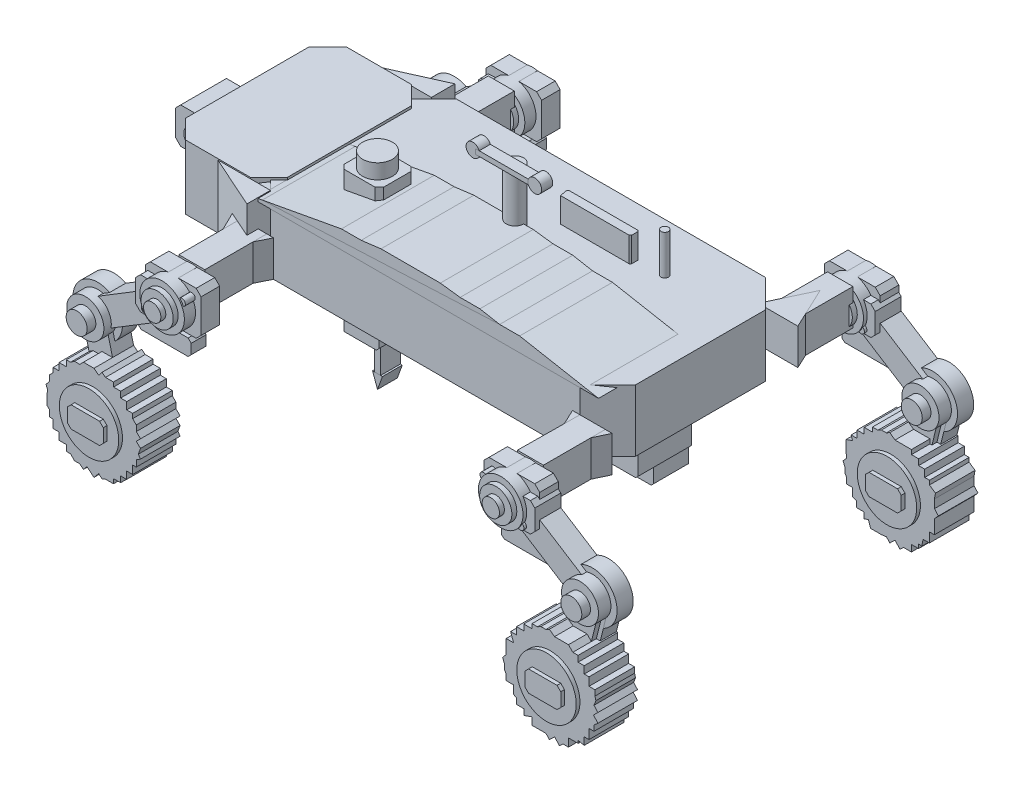
SolidWorks part; units mm, degrees
ref_plane "前视基准面" through (0, 0, 0) normal (0, 0, 1) x (1, 0, 0)
ref_plane "上视基准面" through (0, 0, 0) normal (0, 1, 0) x (1, 0, 0)
ref_plane "右视基准面" through (0, 0, 0) normal (1, 0, 0) x (0, 0, -1)
other "Configuration Table"
ref_plane "v5_near_side_wheel_leg_plane" through (0, 0, 250) normal (0, 0, 1) x (1, 0, 0)
ref_plane "v5_far_side_wheel_leg_plane" through (0, 0, 0) normal (0, 0, 1) x (1, 0, 0)
sketch "草图1" plane through (0, 0, 0) normal (0, 1, 0) x (1, 0, 0)
  line L0 (-225, -150) -> (275, -150)
  line L1 (275, -150) -> (320, -105)
  line L2 (320, -105) -> (320, 105)
  line L3 (320, 105) -> (275, 150)
  line L4 (275, 150) -> (-225, 150)
  line L5 (-225, 150) -> (-270, 105)
  line L6 (-270, 105) -> (-270, -105)
  line L7 (-270, -105) -> (-225, -150)
extrude "v5_1_thicker_chamfered_main_chassis" add sketch "草图1" along normal blind 100 separate body
sketch "草图2" plane through (0, 0, 0) normal (0, 1, 0) x (1, 0, 0)
  line L0 (-382.5, -130) -> (-277.5, -130)
  line L1 (-277.5, -130) -> (-247.5, -100)
  line L2 (-247.5, -100) -> (-247.5, 100)
  line L3 (-247.5, 100) -> (-277.5, 130)
  line L4 (-277.5, 130) -> (-382.5, 130)
  line L5 (-382.5, 130) -> (-412.5, 100)
  line L6 (-412.5, 100) -> (-412.5, -100)
  line L7 (-412.5, -100) -> (-382.5, -130)
extrude "v5_1_projecting_front_sensor_head" add sketch "草图2" along normal blind 104 separate body
sketch "草图3" plane through (0, 0, 0) normal (0, 1, 0) x (1, 0, 0)
  line L0 (-330, 130) -> (-245, 130)
  line L1 (-277.5, 130) -> (-382.5, 130) construction
  line L2 (-225, 150) -> (-270, 105) construction
  line L3 (-245, 130) -> (-245, 168)
  line L4 (-245, 168) -> (-330, 130)
extrude "v5_7_front_near_shoulder_diagonal_fill_no_gap" add sketch "草图3" along normal blind 102 separate body
sketch "草图4" plane through (0, 0, 0) normal (0, 1, 0) x (1, 0, 0)
  line L0 (-330, -130) -> (-245, -130)
  line L1 (-382.5, -130) -> (-277.5, -130) construction
  line L2 (-270, -105) -> (-225, -150) construction
  line L3 (-245, -130) -> (-245, -168)
  line L4 (-245, -168) -> (-330, -130)
extrude "v5_7_front_far_shoulder_diagonal_fill_no_gap" add sketch "草图4" along normal blind 102 separate body
sketch "草图5" plane through (0, 0, 0) normal (0, 1, 0) x (1, 0, 0)
  line L0 (-273, 150) -> (-231, 150)
  line L1 (-231, 150) -> (-231, 250)
  line L2 (-231, 250) -> (-273, 250)
  line L3 (-273, 250) -> (-273, 150)
extrude "v5_17_front_near_side_100mm_outboard_beam_connected" add sketch "草图5" along normal blind 58 separate body
sketch "草图6" plane through (0, 0, 0) normal (0, 1, 0) x (1, 0, 0)
  line L0 (275, 150) -> (316, 150)
  line L1 (316, 150) -> (316, 250)
  line L2 (316, 250) -> (275, 250)
  line L3 (275, 250) -> (275, 150)
extrude "v5_17_rear_near_side_100mm_outboard_beam_connected" add sketch "草图6" along normal blind 58 separate body
sketch "草图7" plane through (0, 0, 0) normal (0, 1, 0) x (1, 0, 0)
  line L0 (-273, -250) -> (-231, -250)
  line L1 (-263.525, -250) -> (263.525, -250) construction
  line L2 (-231, -250) -> (-231, -150)
  line L3 (-231, -150) -> (-273, -150)
  line L4 (-273, -150) -> (-273, -250)
extrude "v5_17_front_far_side_100mm_outboard_beam_connected" add sketch "草图7" along normal blind 58 separate body
sketch "草图8" plane through (0, 0, 0) normal (0, 1, 0) x (1, 0, 0)
  line L0 (274, -250) -> (316, -250)
  line L1 (-263.525, -250) -> (263.525, -250) construction
  line L2 (316, -250) -> (316, -150)
  line L3 (316, -150) -> (275, -150)
  line L4 (275, -150) -> (274, -250)
extrude "v5_17_rear_far_side_100mm_outboard_beam_connected" add sketch "草图8" along normal blind 58 separate body
sketch "草图9" plane through (0, 0, 0) normal (0, 1, 0) x (1, 0, 0)
  line L0 (-287.5, 149) -> (-220, 150)
  line L1 (-245, 168) -> (-330, 130) construction
  line L2 (275, 150) -> (-225, 150) construction
  line L3 (-220, 150) -> (-253.75, 218)
  line L4 (-253.75, 218) -> (-287.5, 149)
extrude "v5_13_front_near_side_compact_root_gusset" add sketch "草图9" along normal blind 58 separate body
sketch "草图10" plane through (0, 0, 0) normal (0, 1, 0) x (1, 0, 0)
  line L0 (263, 150) -> (327, 150)
  line L1 (275, 150) -> (-225, 150) construction
  line L2 (327, 150) -> (295, 218)
  line L3 (295, 218) -> (263, 150)
extrude "v5_13_rear_near_side_compact_root_gusset" add sketch "草图10" along normal blind 58 separate body
sketch "草图11" plane through (0, 0, 0) normal (0, 1, 0) x (1, 0, 0)
  line L0 (-287.5, -149) -> (-220, -150)
  line L1 (-330, -130) -> (-245, -168) construction
  line L2 (-225, -150) -> (275, -150) construction
  line L3 (-220, -150) -> (-253.75, -218)
  line L4 (-253.75, -218) -> (-287.5, -149)
extrude "v5_13_front_far_side_compact_root_gusset" add sketch "草图11" along normal blind 58 separate body
sketch "草图12" plane through (0, 0, 0) normal (0, 1, 0) x (1, 0, 0)
  line L0 (263, -150) -> (327, -150)
  line L1 (-225, -150) -> (275, -150) construction
  line L2 (327, -150) -> (295, -218)
  line L3 (295, -218) -> (263, -150)
extrude "v5_13_rear_far_side_compact_root_gusset" add sketch "草图12" along normal blind 58 separate body
sketch "草图13" plane through (0, 0, 0) normal (0, 0, 1) x (1, 0, 0)
  line L0 (-270, 96) -> (305, 96)
  line L1 (305, 96) -> (273.0556, 101.904)
  line L2 (273.0556, 101.904) -> (241.1432, 107.8022)
  line L3 (241.1432, 107.8022) -> (209.2939, 113.6886)
  line L4 (209.2939, 113.6886) -> (177.537, 119.558)
  line L5 (177.537, 119.558) -> (145.2778, 119.558)
  line L6 (145.2778, 119.558) -> (113.3333, 125.4449)
  line L7 (113.3333, 125.4449) -> (81.3889, 125.4449)
  line L8 (81.3889, 125.4449) -> (49.4444, 129.4835)
  line L9 (49.4444, 129.4835) -> (17.5, 129.4835)
  line L10 (17.5, 129.4835) -> (-14.4444, 129.4835)
  line L11 (-14.4444, 129.4835) -> (-46.3889, 129.4835)
  line L12 (-46.3889, 129.4835) -> (-78.3333, 125.4449)
  line L13 (-78.3333, 125.4449) -> (-110.2778, 125.4449)
  line L14 (-110.2778, 125.4449) -> (-142.2222, 119.558)
  line L15 (-142.2222, 119.558) -> (-174.0716, 113.6886)
  line L16 (-174.0716, 113.6886) -> (-206.0136, 107.8022)
  line L17 (-206.0136, 107.8022) -> (-238.019, 101.904)
  line L18 (-238.019, 101.904) -> (-270, 96)
extrude "v5_1_near_segmented_curved_upper_shell" add sketch "草图13" along normal blind 150 separate body
sketch "草图14" plane through (0, 0, 0) normal (0, 0, 1) x (1, 0, 0)
  line L0 (-270, 96) -> (305, 96)
  line L1 (305, 96) -> (273.0556, 101.904)
  line L2 (305, 96) -> (177.537, 119.558) construction
  line L3 (273.0556, 101.904) -> (241.2685, 107.779)
  line L4 (241.2685, 107.779) -> (209.2939, 113.6886)
  line L5 (209.2939, 113.6886) -> (177.537, 119.558)
  line L6 (177.537, 119.558) -> (145.2778, 119.558)
  line L7 (145.2778, 119.558) -> (113.3333, 125.4449)
  line L8 (113.3333, 125.4449) -> (81.3889, 125.4449)
  line L9 (81.3889, 125.4449) -> (49.4444, 129.4835)
  line L10 (49.4444, 129.4835) -> (17.5, 129.4835)
  line L11 (49.4444, 129.4835) -> (-46.3889, 129.4835) construction
  line L12 (17.5, 129.4835) -> (-14.4444, 129.4835)
  line L13 (-14.4444, 129.4835) -> (-46.3889, 129.4835)
  line L14 (-46.3889, 129.4835) -> (-78.3333, 125.4449)
  line L15 (-78.3333, 125.4449) -> (-110.2778, 125.4449)
  line L16 (-110.2778, 125.4449) -> (-142.2222, 119.558)
  line L17 (-110.2778, 125.4449) -> (-238.019, 101.904) construction
  line L18 (-142.2222, 119.558) -> (-174.1484, 113.6745)
  line L19 (-174.1484, 113.6745) -> (-206.1393, 107.779)
  line L20 (-206.1393, 107.779) -> (-238.019, 101.904)
  line L21 (-238.019, 101.904) -> (-270, 96)
extrude "v5_1_far_segmented_curved_upper_shell" add sketch "草图14" along normal blind 150 flip side to cut separate body
sketch "草图15" plane through (0, 0, 0) normal (0, 0, 1) x (1, 0, 0)
  line L0 (10.5, 14) -> (199.5, 14)
  line L1 (199.5, 14) -> (207.5, 22)
  line L2 (207.5, 22) -> (207.5, 82)
  line L3 (207.5, 82) -> (199.5, 90)
  line L4 (199.5, 90) -> (10.5, 90)
  line L5 (10.5, 90) -> (0, 79.5)
  line L6 (0, 79.5) -> (0, 22)
  line L7 (0, 22) -> (10.5, 14)
extrude "v5_1_recessed_side_panel_frame" add sketch "草图15" along normal blind 74 separate body
sketch "草图16" plane through (0, 0, 0) normal (0, 0, 1) x (1, 0, 0)
  line L0 (31, 28) -> (179, 28)
  line L1 (179, 28) -> (184, 33)
  line L2 (184, 33) -> (184, 75)
  line L3 (184, 75) -> (179, 80)
  line L4 (179, 80) -> (31, 80)
  line L5 (31, 80) -> (26, 75)
  line L6 (26, 75) -> (26, 33)
  line L7 (26, 33) -> (31, 28)
extrude "v5_1_battery_electronics_panel_insert" add sketch "草图16" along normal blind 82 separate body
sketch "草图17" plane through (0, 0, 0) normal (0, 0, 1) x (1, 0, 0)
  line L0 (-191, -49) -> (301, -49)
  line L1 (301, -49) -> (305, -45)
  line L2 (305, -45) -> (305, 9)
  line L3 (305, 9) -> (301, 13)
  line L4 (301, 13) -> (-191, 13)
  line L5 (-191, 13) -> (-195, 9)
  line L6 (-195, 9) -> (-195, -45)
  line L7 (-195, -45) -> (-191, -49)
extrude "v5_7_integrated_lower_side_skirt_no_long_gap" add sketch "草图17" along normal blind 86
sketch "草图18" plane through (0, 0, 0) normal (0, 0, 1) x (1, 0, 0)
  line L0 (-135, -76) -> (15, -76)
  line L1 (15, -76) -> (20, -71)
  line L2 (20, -71) -> (20, -37)
  line L3 (20, -37) -> (15, -32)
  line L4 (15, -32) -> (-135, -32)
  line L5 (-135, -32) -> (-140, -37)
  line L6 (-140, -37) -> (-140, -71)
  line L7 (-140, -71) -> (-135, -76)
extrude "v5_7_protected_underbody_payload_bay_joined" add sketch "草图18" along normal blind 60
sketch "草图19" plane through (0, 0, 0) normal (0, 0, 1) x (1, 0, 0)
  line L0 (-181, -77) -> (-159, -77)
  line L1 (-159, -77) -> (-155, -73)
  line L2 (-155, -73) -> (-155, -15)
  line L3 (-155, -15) -> (-159, -11)
  line L4 (-159, -11) -> (-181, -11)
  line L5 (-181, -11) -> (-185, -15)
  line L6 (-185, -15) -> (-185, -73)
  line L7 (-185, -73) -> (-181, -77)
extrude "v5_7_front_skid_vertical_support_joined" add sketch "草图19" along normal blind 56
sketch "草图20" plane through (0, 0, 0) normal (0, 0, 1) x (1, 0, 0)
  line L0 (29, -77) -> (51, -77)
  line L1 (51, -77) -> (55, -73)
  line L2 (55, -73) -> (55, -15)
  line L3 (55, -15) -> (51, -11)
  line L4 (51, -11) -> (29, -11)
  line L5 (29, -11) -> (25, -15)
  line L6 (25, -15) -> (25, -73)
  line L7 (25, -73) -> (29, -77)
extrude "v5_7_center_skid_vertical_support_joined" add sketch "草图20" along normal blind 56
sketch "草图21" plane through (0, 0, 0) normal (0, 0, 1) x (1, 0, 0)
  line L0 (274, -77) -> (296, -77)
  line L1 (296, -77) -> (300, -73)
  line L2 (300, -73) -> (300, -15)
  line L3 (300, -15) -> (296, -11)
  line L4 (296, -11) -> (274, -11)
  line L5 (274, -11) -> (270, -15)
  line L6 (270, -15) -> (270, -73)
  line L7 (270, -73) -> (274, -77)
extrude "v5_7_rear_skid_vertical_support_joined" add sketch "草图21" along normal blind 56
sketch "草图22" plane through (0, 0, 0) normal (0, 0, 1) x (1, 0, 0)
  line L0 (-446, 35) -> (-338, 35)
  line L1 (-338, 35) -> (-330, 43)
  line L2 (-330, 43) -> (-330, 85)
  line L3 (-330, 85) -> (-338, 93)
  line L4 (-338, 93) -> (-446, 93)
  line L5 (-446, 93) -> (-454, 85)
  line L6 (-454, 85) -> (-454, 43)
  line L7 (-454, 43) -> (-446, 35)
extrude "v5_1_front_stereo_camera_bezel" add sketch "草图22" along normal blind 74 separate body
sketch "草图23" plane through (0, 0, 0) normal (0, 0, 1) x (1, 0, 0)
  circle A0 centre (-416, 66) radius 15
extrude "v5_1_left_rgb_camera_lens" add sketch "草图23" along normal blind 84 separate body
sketch "草图24" plane through (0, 0, 0) normal (0, 0, 1) x (1, 0, 0)
  circle A0 centre (-370, 66) radius 15
extrude "v5_1_right_depth_camera_lens" add sketch "草图24" along normal blind 84 separate body
sketch "草图25" plane through (0, 0, 250) normal (0, 0, 1) x (1, 0, 0)
  line L0 (-289, -15) -> (-215, -15)
  line L1 (-215, -15) -> (-207, -7)
  line L2 (-207, -7) -> (-207, 47)
  line L3 (-207, 47) -> (-215, 55)
  line L4 (-215, 55) -> (-289, 55)
  line L5 (-289, 55) -> (-297, 47)
  line L6 (-297, 47) -> (-297, -7)
  line L7 (-297, -7) -> (-289, -15)
extrude "front_near_leg_side_hip_mount_plate" add sketch "草图25" along normal blind 30 separate body
sketch "草图26" plane through (0, 0, 250) normal (0, 0, 1) x (1, 0, 0)
  line L0 (-293, -11) -> (-246, -11)
  line L1 (-297, -7) -> (-289, -15) construction
  line L2 (-246, -11) -> (-238, -3)
  line L3 (-238, -3) -> (-238, 33)
  line L4 (-238, 33) -> (-246, 41)
  line L5 (-246, 41) -> (-293, 41)
  line L6 (-293, 41) -> (-301, 33)
  line L7 (-301, 33) -> (-301, -3)
  line L8 (-301, -3) -> (-293, -11)
extrude "front_near_leg_side_fork_clevis_block" add sketch "草图26" along normal blind 42 separate body
sketch "草图27" plane through (0, 0, 250) normal (0, 0, 1) x (1, 0, 0)
  line L0 (-310, -53) -> (-234, -53)
  line L1 (-234, -53) -> (-229, -48)
  line L2 (-229, -48) -> (-229, -32)
  line L3 (-229, -32) -> (-234, -27)
  line L4 (-234, -27) -> (-310, -27)
  line L5 (-310, -27) -> (-315, -32)
  line L6 (-315, -32) -> (-315, -48)
  line L7 (-315, -48) -> (-310, -53)
extrude "front_near_leg_side_chamfered_gusset_block" add sketch "草图27" along normal blind 24 separate body
sketch "草图28" plane through (0, 0, 250) normal (0, 0, 1) x (1, 0, 0)
  circle A0 centre (-222, 40) radius 5.5
extrude "front_near_leg_side_upper_mount_bolt" add sketch "草图28" along normal blind 46 separate body
sketch "草图29" plane through (0, 0, 250) normal (0, 0, 1) x (1, 0, 0)
  circle A0 centre (-282, 0) radius 5.5
extrude "front_near_leg_side_lower_mount_bolt" add sketch "草图29" along normal blind 46 separate body
sketch "草图30" plane through (0, 0, 250) normal (0, 0, 1) x (1, 0, 0)
  line L0 (-241.2798, 0) -> (-367.2798, -76.8843)
  line L1 (-367.2798, -76.8843) -> (-388.1117, -42.7445)
  line L2 (-388.1117, -42.7445) -> (-261.3348, 34.6139)
  line L3 (-261.3348, 34.6139) -> (-241.2798, 0)
extrude "front_near_leg_side_upper_parallel_link" add sketch "草图30" along normal blind 34 separate body
sketch "草图31" plane through (0, 0, 250) normal (0, 0, 1) x (1, 0, 0)
  line L0 (-262.1759, 0) -> (-388.1759, -77.5979)
  line L1 (-388.1759, -77.5979) -> (-397.614, -62.2727)
  line L2 (-397.614, -62.2727) -> (-270.7515, 15.8564)
  line L3 (-270.7515, 15.8564) -> (-262.1759, 0)
extrude "front_near_leg_side_inner_upper_link" add sketch "草图31" along normal blind 26 separate body
sketch "草图32" plane through (0, 0, 250) normal (0, 0, 1) x (1, 0, 0)
  line L0 (-358.5971, -55.1493) -> (-328.5971, -175.1493)
  line L1 (-328.5971, -175.1493) -> (-367.4029, -184.8507)
  line L2 (-367.4029, -184.8507) -> (-396.4049, -64.2361)
  line L3 (-397.614, -62.2727) -> (-388.1759, -77.5979) construction
  line L4 (-396.4049, -64.2361) -> (-358.5971, -55.1493)
extrude "front_near_leg_side_lower_parallel_link" add sketch "草图32" along normal blind 34 separate body
sketch "草图33" plane through (0, 0, 250) normal (0, 0, 1) x (1, 0, 0)
  line L0 (-384.2687, -67.8172) -> (-354.2687, -187.8172)
  line L1 (-354.2687, -187.8172) -> (-369.2687, -191.5672)
  line L2 (-369.2687, -191.5672) -> (-399.2687, -71.5672)
  line L3 (-399.2687, -71.5672) -> (-384.2687, -67.8172)
extrude "front_near_leg_side_inner_lower_link" add sketch "草图33" along normal blind 26 separate body
sketch "草图34" plane through (0, 0, 250) normal (0, 0, 1) x (1, 0, 0)
  circle A0 centre (-252, 20) radius 36
extrude "front_near_leg_side_hip_joint_pod" add sketch "草图34" along normal blind 48 separate body
sketch "草图35" plane through (0, 0, 250) normal (0, 0, 1) x (1, 0, 0)
  circle A0 centre (-252, 20) radius 26
extrude "front_near_leg_side_hip_angle_control_washer" add sketch "草图35" along normal blind 56 separate body
sketch "草图36" plane through (0, 0, 250) normal (0, 0, 1) x (1, 0, 0)
  circle A0 centre (-252, 20) radius 14
extrude "front_near_leg_side_hip_pin_cap" add sketch "草图36" along normal blind 64 separate body
sketch "草图37" plane through (0, 0, 250) normal (0, 0, 1) x (1, 0, 0)
  circle A0 centre (-378, -60) radius 30
extrude "front_near_leg_side_knee_joint_pod" add sketch "草图37" along normal blind 46 separate body
sketch "草图38" plane through (0, 0, 250) normal (0, 0, 1) x (1, 0, 0)
  circle A0 centre (-378, -60) radius 40
extrude "front_near_leg_side_knee_outer_angle_plate" add sketch "草图38" along normal blind 26 separate body
sketch "草图39" plane through (0, 0, 250) normal (0, 0, 1) x (1, 0, 0)
  circle A0 centre (-378, -60) radius 17
extrude "front_near_leg_side_knee_pin_cap" add sketch "草图39" along normal blind 60 separate body
sketch "草图40" plane through (0, 0, 250) normal (0, 0, 1) x (1, 0, 0)
  line L0 (-367.4029, -184.8507) -> (-328.5971, -175.1493) construction
  circle A0 centre (-348, -180) radius 30
extrude "front_near_leg_side_axle_joint_pod" add sketch "草图40" along normal blind 46 separate body
sketch "草图41" plane through (0, 0, 250) normal (0, 0, 1) x (1, 0, 0)
  circle A0 centre (-348, -180) radius 21
extrude "front_near_leg_side_axle_pin_cap" add sketch "草图41" along normal blind 58 separate body
sketch "草图42" plane through (0, 0, 250) normal (0, 0, 1) x (1, 0, 0)
  line L0 (-271, -180) -> (-277.6506, -173.3494)
  line L1 (-277.6506, -173.3494) -> (-270.8793, -166.5782)
  line L2 (-270.8793, -166.5782) -> (-277.6506, -159.807)
  line L3 (-277.6506, -159.807) -> (-277.6506, -150.5334)
  line L4 (-277.6506, -150.5334) -> (-283.5183, -144.6656)
  line L5 (-283.5183, -144.6656) -> (-283.5183, -137.2211)
  line L6 (-283.5183, -137.2211) -> (-293.1163, -137.2211)
  line L7 (-293.1163, -137.2211) -> (-293.1163, -125.5528)
  line L8 (-293.1163, -125.5528) -> (-302.9581, -125.5528)
  line L9 (-302.9581, -125.5528) -> (-302.9581, -115.9768)
  line L10 (-302.9581, -115.9768) -> (-314.5308, -115.9768)
  line L11 (-314.5308, -115.9768) -> (-314.5308, -108.8613)
  line L12 (-314.5308, -108.8613) -> (-327.3898, -108.8613)
  line L13 (-327.3898, -108.8613) -> (-332.978, -104.4795)
  line L14 (-332.978, -104.4795) -> (-338.4088, -111.4056)
  line L15 (-338.4088, -111.4056) -> (-346.0263, -105.4328)
  line L16 (-328.5971, -175.1493) -> (-358.5971, -55.1493) construction
  line L17 (-346.0263, -105.4328) -> (-354.9592, -105.4328)
  line L18 (-354.9592, -105.4328) -> (-363.022, -105.4328)
  line L19 (-363.022, -105.4328) -> (-368.9948, -111.4056)
  line L20 (-368.9948, -111.4056) -> (-377.4666, -111.4056)
  line L21 (-377.4666, -111.4056) -> (-383.9637, -115.9768)
  line L22 (-396.4049, -64.2361) -> (-367.4029, -184.8507) construction
  line L23 (-383.9637, -115.9768) -> (-390.7789, -115.9768)
  line L24 (-390.7789, -115.9768) -> (-390.7789, -125.5528)
  line L25 (-390.7789, -125.5528) -> (-402.4472, -125.5528)
  line L26 (-402.4472, -125.5528) -> (-402.4472, -137.2211)
  line L27 (-402.4472, -137.2211) -> (-412.0232, -137.2211)
  line L28 (-412.0232, -137.2211) -> (-412.0232, -144.6656)
  line L29 (-412.0232, -144.6656) -> (-417.891, -150.5334)
  line L30 (-417.891, -150.5334) -> (-417.891, -159.807)
  line L31 (-417.891, -159.807) -> (-423.5205, -166.5782)
  line L32 (-423.5205, -166.5782) -> (-420.7057, -173.3494)
  line L33 (-420.7057, -173.3494) -> (-422.1131, -180)
  line L34 (-422.1131, -180) -> (-422.1131, -186.9592)
  line L35 (-422.1131, -186.9592) -> (-422.1131, -195.022)
  line L36 (-422.1131, -195.022) -> (-417.891, -199.2441)
  line L37 (-417.891, -199.2441) -> (-417.891, -209.4666)
  line L38 (-417.891, -209.4666) -> (-412.0232, -209.4666)
  line L39 (-412.0232, -209.4666) -> (-412.0232, -222.7789)
  line L40 (-412.0232, -222.7789) -> (-402.4472, -222.7789)
  line L41 (-402.4472, -222.7789) -> (-402.4472, -234.4472)
  line L42 (-402.4472, -234.4472) -> (-390.7789, -234.4472)
  line L43 (-390.7789, -234.4472) -> (-390.7789, -244.0232)
  line L44 (-390.7789, -244.0232) -> (-383.9637, -244.0232)
  line L45 (-383.9637, -244.0232) -> (-377.4666, -250.5203)
  line L46 (-377.4666, -250.5203) -> (-368.9948, -250.5203)
  line L47 (-368.9948, -250.5203) -> (-363.022, -255.5205)
  line L48 (-363.022, -255.5205) -> (-357.3064, -248.6931)
  line L49 (-357.3064, -248.6931) -> (-346.0263, -258.1364)
  line L50 (-346.0263, -258.1364) -> (-338.4088, -249.0371)
  line L51 (-338.4088, -249.0371) -> (-332.978, -253.5835)
  line L52 (-332.978, -253.5835) -> (-327.3898, -251.3103)
  line L53 (-327.3898, -251.3103) -> (-314.5308, -251.3103)
  line L54 (-314.5308, -251.3103) -> (-314.5308, -244.0232)
  line L55 (-314.5308, -244.0232) -> (-302.9581, -244.0232)
  line L56 (-302.9581, -244.0232) -> (-302.9581, -234.4472)
  line L57 (-302.9581, -234.4472) -> (-293.1163, -234.4472)
  line L58 (-293.1163, -234.4472) -> (-293.1163, -222.7789)
  line L59 (-293.1163, -222.7789) -> (-283.5183, -222.7789)
  line L60 (-283.5183, -222.7789) -> (-283.5183, -209.4666)
  line L61 (-283.5183, -209.4666) -> (-277.6506, -209.4666)
  line L62 (-277.6506, -209.4666) -> (-277.6506, -199.2441)
  line L63 (-277.6506, -199.2441) -> (-271, -195.022)
  line L64 (-271, -195.022) -> (-274.3253, -189.7841)
  line L65 (-274.3253, -189.7841) -> (-271, -180)
extrude "front_near_leg_side_mounted_block_tread_tire" add sketch "草图42" along normal blind 64 separate body
sketch "草图43" plane through (0, 0, 250) normal (0, 0, 1) x (1, 0, 0)
  circle A0 centre (-348, -180) radius 48
extrude "front_near_leg_side_silver_hub_disc" add sketch "草图43" along normal blind 70 separate body
sketch "草图44" plane through (0, 0, 250) normal (0, 0, 1) x (1, 0, 0)
  line L0 (-371, -197) -> (-325, -197)
  line L1 (-325, -197) -> (-319, -191)
  line L2 (-319, -191) -> (-319, -169)
  line L3 (-319, -169) -> (-325, -163)
  line L4 (-325, -163) -> (-371, -163)
  line L5 (-371, -163) -> (-377, -169)
  line L6 (-377, -169) -> (-377, -191)
  line L7 (-377, -191) -> (-371, -197)
extrude "front_near_leg_side_rectangular_hub_cap" add sketch "草图44" along normal blind 76 separate body
sketch "草图45" plane through (0, 0, 250) normal (0, 0, 1) x (1, 0, 0)
  line L0 (258, -15) -> (332, -15)
  line L1 (332, -15) -> (340, -7)
  line L2 (340, -7) -> (340, 47)
  line L3 (340, 47) -> (332, 55)
  line L4 (332, 55) -> (258, 55)
  line L5 (258, 55) -> (250, 47)
  line L6 (250, 47) -> (250, -7)
  line L7 (250, -7) -> (258, -15)
extrude "rear_near_leg_side_hip_mount_plate" add sketch "草图45" along normal blind 30 separate body
sketch "草图46" plane through (0, 0, 250) normal (0, 0, 1) x (1, 0, 0)
  line L0 (289, -7) -> (337, -7)
  line L1 (337, -7) -> (344, 0)
  line L2 (344, 0) -> (344, 33)
  line L3 (344, 33) -> (337, 40)
  line L4 (337, 40) -> (289, 40)
  line L5 (289, 40) -> (282, 33)
  line L6 (282, 33) -> (282, 0)
  line L7 (282, 0) -> (289, -7)
extrude "rear_near_leg_side_fork_clevis_block" add sketch "草图46" along normal blind 42 separate body
sketch "草图47" plane through (0, 0, 250) normal (0, 0, 1) x (1, 0, 0)
  line L0 (277, -53) -> (353, -53)
  line L1 (353, -53) -> (358, -48)
  line L2 (358, -48) -> (358, -32)
  line L3 (358, -32) -> (353, -27)
  line L4 (353, -27) -> (277, -27)
  line L5 (277, -27) -> (272, -32)
  line L6 (272, -32) -> (272, -49)
  line L7 (-191, -49) -> (301, -49) construction
  line L8 (272, -49) -> (277, -53)
extrude "rear_near_leg_side_chamfered_gusset_block" add sketch "草图47" along normal blind 24 separate body
sketch "草图48" plane through (0, 0, 250) normal (0, 0, 1) x (1, 0, 0)
  circle A0 centre (265, 40) radius 5.5
extrude "rear_near_leg_side_upper_mount_bolt" add sketch "草图48" along normal blind 46 separate body
sketch "草图49" plane through (0, 0, 250) normal (0, 0, 1) x (1, 0, 0)
  circle A0 centre (325, 0) radius 5.5
extrude "rear_near_leg_side_lower_mount_bolt" add sketch "草图49" along normal blind 46 separate body
sketch "草图50" plane through (0, 0, 250) normal (0, 0, 1) x (1, 0, 0)
  line L0 (305.7202, 36.8843) -> (431.7202, -43.1157)
  line L1 (431.7202, -43.1157) -> (410.2798, -76.8843)
  line L2 (410.2798, -76.8843) -> (282, 4.5633)
  line L3 (282, 33) -> (282, 0) construction
  line L4 (282, 4.5633) -> (305.7202, 36.8843)
extrude "rear_near_leg_side_upper_parallel_link" add sketch "草图50" along normal blind 34 separate body
sketch "草图51" plane through (0, 0, 250) normal (0, 0, 1) x (1, 0, 0)
  line L0 (314.8241, 17.5979) -> (440.8241, -62.4021)
  line L1 (440.8241, -62.4021) -> (431.1759, -77.5979)
  line L2 (431.1759, -77.5979) -> (308.9592, 0)
  line L3 (308.9592, 0) -> (314.8241, 17.5979)
extrude "rear_near_leg_side_inner_upper_link" add sketch "草图51" along normal blind 26 separate body
sketch "草图52" plane through (0, 0, 250) normal (0, 0, 1) x (1, 0, 0)
  line L0 (440.8241, -62.4021) -> (410.4029, -184.8507)
  line L1 (410.4029, -184.8507) -> (371.583, -175.2063)
  line L2 (371.583, -175.2063) -> (401.4209, -55.1055)
  line L3 (401.4209, -55.1055) -> (440.8241, -62.4021)
extrude "rear_near_leg_side_lower_parallel_link" add sketch "草图52" along normal blind 34 separate body
sketch "草图53" plane through (0, 0, 250) normal (0, 0, 1) x (1, 0, 0)
  line L0 (444.7313, -72.1828) -> (414.7313, -192.1828)
  line L1 (414.7313, -192.1828) -> (397.2687, -192.1828)
  line L2 (397.2687, -192.1828) -> (427.2687, -72.1828)
  line L3 (427.2687, -72.1828) -> (444.7313, -72.1828)
extrude "rear_near_leg_side_inner_lower_link" add sketch "草图53" along normal blind 26 separate body
sketch "草图54" plane through (0, 0, 250) normal (0, 0, 1) x (1, 0, 0)
  circle A0 centre (295, 20) radius 36
extrude "rear_near_leg_side_hip_joint_pod" add sketch "草图54" along normal blind 48 separate body
sketch "草图55" plane through (0, 0, 250) normal (0, 0, 1) x (1, 0, 0)
  circle A0 centre (295, 20) radius 26
extrude "rear_near_leg_side_hip_angle_control_washer" add sketch "草图55" along normal blind 56 separate body
sketch "草图56" plane through (0, 0, 250) normal (0, 0, 1) x (1, 0, 0)
  circle A0 centre (295, 20) radius 14
extrude "rear_near_leg_side_hip_pin_cap" add sketch "草图56" along normal blind 64 separate body
sketch "草图57" plane through (0, 0, 250) normal (0, 0, 1) x (1, 0, 0)
  line L0 (440.8241, -62.4021) -> (401.4209, -55.1055) construction
  circle A0 centre (421.1225, -58.7538) radius 29.8775
extrude "rear_near_leg_side_knee_joint_pod" add sketch "草图57" along normal blind 46 separate body
sketch "草图58" plane through (0, 0, 250) normal (0, 0, 1) x (1, 0, 0)
  circle A0 centre (421, -60) radius 40
extrude "rear_near_leg_side_knee_outer_angle_plate" add sketch "草图58" along normal blind 26 separate body
sketch "草图59" plane through (0, 0, 250) normal (0, 0, 1) x (1, 0, 0)
  circle A0 centre (421, -60) radius 17
extrude "rear_near_leg_side_knee_pin_cap" add sketch "草图59" along normal blind 60 separate body
sketch "草图60" plane through (0, 0, 250) normal (0, 0, 1) x (1, 0, 0)
  line L0 (371.583, -175.2063) -> (410.4029, -184.8507) construction
  circle A0 centre (390.9929, -180.0285) radius 30.0071
extrude "rear_near_leg_side_axle_joint_pod" add sketch "草图60" along normal blind 46 separate body
sketch "草图61" plane through (0, 0, 250) normal (0, 0, 1) x (1, 0, 0)
  circle A0 centre (391, -180) radius 21
extrude "rear_near_leg_side_axle_pin_cap" add sketch "草图61" along normal blind 58 separate body
sketch "草图62" plane through (0, 0, 250) normal (0, 0, 1) x (1, 0, 0)
  line L0 (468, -180) -> (461.6581, -173.0408)
  line L1 (461.6581, -173.0408) -> (464.8291, -164.978)
  line L2 (464.8291, -164.978) -> (463.2436, -159.3898)
  line L3 (463.2436, -159.3898) -> (463.2436, -150.5334)
  line L4 (463.2436, -150.5334) -> (453.6164, -150.5334)
  line L5 (453.6164, -150.5334) -> (453.6164, -137.2211)
  line L6 (453.6164, -137.2211) -> (445.8837, -137.2211)
  line L7 (445.8837, -137.2211) -> (445.8837, -125.5528)
  line L8 (445.8837, -125.5528) -> (436.0419, -125.5528)
  line L9 (436.0419, -125.5528) -> (436.0419, -115.9768)
  line L10 (436.0419, -115.9768) -> (427.5139, -115.9768)
  line L11 (410.4029, -184.8507) -> (440.8241, -62.4021) construction
  line L12 (427.5139, -115.9768) -> (420.4325, -108.8954)
  line L13 (420.4325, -108.8954) -> (411.6102, -108.8954)
  line L14 (411.6102, -108.8954) -> (406.022, -108.8954)
  line L15 (406.022, -108.8954) -> (397.9592, -108.8954)
  line L16 (397.9592, -108.8954) -> (389.6079, -102.6541)
  line L17 (401.4209, -55.1055) -> (371.583, -175.2063) construction
  line L18 (389.6079, -102.6541) -> (384.0408, -105.7748)
  line L19 (384.0408, -105.7748) -> (375.978, -105.7748)
  line L20 (375.978, -105.7748) -> (370.3898, -108.8954)
  line L21 (370.3898, -108.8954) -> (361.5334, -108.8954)
  line L22 (361.5334, -108.8954) -> (361.5334, -115.9768)
  line L23 (361.5334, -115.9768) -> (348.2211, -115.9768)
  line L24 (348.2211, -115.9768) -> (348.2211, -125.5528)
  line L25 (348.2211, -125.5528) -> (336.5528, -125.5528)
  line L26 (336.5528, -125.5528) -> (336.5528, -137.2211)
  line L27 (336.5528, -137.2211) -> (326.9768, -137.2211)
  line L28 (326.9768, -137.2211) -> (331.7648, -150.5334)
  line L29 (331.7648, -150.5334) -> (319.8613, -150.5334)
  line L30 (319.8613, -150.5334) -> (319.8613, -159.3898)
  line L31 (319.8613, -159.3898) -> (319.8613, -164.978)
  line L32 (319.8613, -164.978) -> (319.8613, -173.0408)
  line L33 (319.8613, -173.0408) -> (314, -180)
  line L34 (314, -180) -> (316.9306, -186.9592)
  line L35 (316.9306, -186.9592) -> (316.9306, -195.022)
  line L36 (316.9306, -195.022) -> (319.8613, -200.6102)
  line L37 (319.8613, -200.6102) -> (319.8613, -209.4666)
  line L38 (319.8613, -209.4666) -> (331.7648, -209.4666)
  line L39 (331.7648, -209.4666) -> (331.7648, -222.7789)
  line L40 (331.7648, -222.7789) -> (336.1163, -225.0419)
  line L41 (336.1163, -225.0419) -> (336.1163, -234.4472)
  line L42 (336.1163, -234.4472) -> (348.2211, -234.4472)
  line L43 (348.2211, -234.4472) -> (348.2211, -244.0232)
  line L44 (348.2211, -244.0232) -> (361.5334, -239.2352)
  line L45 (361.5334, -239.2352) -> (361.5334, -251.1387)
  line L46 (361.5334, -251.1387) -> (370.3898, -251.1387)
  line L47 (370.3898, -251.1387) -> (375.978, -251.1387)
  line L48 (375.978, -251.1387) -> (384.0408, -251.1387)
  line L49 (384.0408, -251.1387) -> (389.6079, -257)
  line L50 (389.6079, -257) -> (397.9592, -249.0678)
  line L51 (397.9592, -249.0678) -> (406.022, -257.5566)
  line L52 (406.022, -257.5566) -> (411.6102, -252.2488)
  line L53 (411.6102, -252.2488) -> (420.4325, -252.2488)
  line L54 (420.4325, -252.2488) -> (420.4325, -239.2352)
  line L55 (420.4325, -239.2352) -> (436.0419, -239.2352)
  line L56 (436.0419, -239.2352) -> (436.0419, -234.8837)
  line L57 (436.0419, -234.8837) -> (445.8837, -237.0595)
  line L58 (445.8837, -237.0595) -> (445.8837, -225.0419)
  line L59 (445.8837, -225.0419) -> (453.6164, -225.0419)
  line L60 (453.6164, -225.0419) -> (453.6164, -209.4666)
  line L61 (453.6164, -209.4666) -> (461.6581, -209.4666)
  line L62 (461.6581, -209.4666) -> (461.6581, -200.6102)
  line L63 (461.6581, -200.6102) -> (468, -195.022)
  line L64 (468, -195.022) -> (460.8954, -186.9592)
  line L65 (460.8954, -186.9592) -> (468, -180)
extrude "rear_near_leg_side_mounted_block_tread_tire" add sketch "草图62" along normal blind 64 separate body
sketch "草图63" plane through (0, 0, 250) normal (0, 0, 1) x (1, 0, 0)
  circle A0 centre (391, -180) radius 48
extrude "rear_near_leg_side_silver_hub_disc" add sketch "草图63" along normal blind 70 separate body
sketch "草图64" plane through (0, 0, 250) normal (0, 0, 1) x (1, 0, 0)
  line L0 (368, -197) -> (414, -197)
  line L1 (414, -197) -> (420, -191)
  line L2 (420, -191) -> (420, -169)
  line L3 (420, -169) -> (414, -163)
  line L4 (414, -163) -> (368, -163)
  line L5 (368, -163) -> (362, -169)
  line L6 (362, -169) -> (362, -191)
  line L7 (362, -191) -> (368, -197)
extrude "rear_near_leg_side_rectangular_hub_cap" add sketch "草图64" along normal blind 76 separate body
sketch "草图65" plane through (0, 0, 0) normal (0, 0, 1) x (1, 0, 0)
  line L0 (-289, -15) -> (-215, -15)
  line L1 (-215, -15) -> (-207, -7)
  line L2 (-207, -7) -> (-207, 47)
  line L3 (-207, 47) -> (-215, 55)
  line L4 (-215, 55) -> (-289, 55)
  line L5 (-289, 55) -> (-297, 47)
  line L6 (-297, 47) -> (-297, -7)
  line L7 (-297, -7) -> (-289, -15)
extrude "front_far_leg_side_hip_mount_plate" add sketch "草图65" along normal blind 30 flip side to cut separate body
sketch "草图66" plane through (0, 0, 0) normal (0, 0, 1) x (1, 0, 0)
  line L0 (-297, -7) -> (-246, -7)
  line L1 (-301, -3) -> (-293, -11) construction
  line L2 (-246, -7) -> (-235.3868, 0)
  line L3 (-235.3868, 0) -> (-235.3868, 33)
  line L4 (-235.3868, 33) -> (-246, 43.6132)
  line L5 (-246, 43.6132) -> (-293, 41)
  line L6 (-293, 41) -> (-297, 36.529)
  line L7 (-297, 36.529) -> (-301, -3)
  line L8 (-301, -3) -> (-297, -7)
  circle A0 centre (-252, 20) radius 26 construction
extrude "front_far_leg_side_fork_clevis_block" add sketch "草图66" along normal blind 42 flip side to cut separate body
sketch "草图67" plane through (0, 0, 0) normal (0, 0, 1) x (1, 0, 0)
  line L0 (-310, -53) -> (-234, -53)
  line L1 (-234, -53) -> (-229, -48)
  line L2 (-229, -48) -> (-229, -32)
  line L3 (-229, -32) -> (-234, -27)
  line L4 (-234, -27) -> (-310, -27)
  line L5 (-310, -27) -> (-315, -32)
  line L6 (-315, -32) -> (-315, -48)
  line L7 (-315, -48) -> (-310, -53)
extrude "front_far_leg_side_chamfered_gusset_block" add sketch "草图67" along normal blind 24 flip side to cut separate body
sketch "草图68" plane through (0, 0, 0) normal (0, 0, 1) x (1, 0, 0)
  circle A0 centre (-222.0462, 39.9692) radius 5.5555
  circle A1 centre (-252, 20) radius 36 construction
extrude "front_far_leg_side_upper_mount_bolt" add sketch "草图68" along normal blind 46 flip side to cut separate body
sketch "草图69" plane through (0, 0, 0) normal (0, 0, 1) x (1, 0, 0)
  circle A0 centre (-282, 0) radius 5.5
extrude "front_far_leg_side_lower_mount_bolt" add sketch "草图69" along normal blind 46 flip side to cut separate body
sketch "草图70" plane through (0, 0, 0) normal (0, 0, 1) x (1, 0, 0)
  line L0 (-241.2798, 0) -> (-367.2798, -76.8843)
  line L1 (-367.2798, -76.8843) -> (-388.1117, -42.7445)
  line L2 (-388.1117, -42.7445) -> (-261.3348, 34.6139)
  line L3 (-261.3348, 34.6139) -> (-241.2798, 0)
extrude "front_far_leg_side_upper_parallel_link" add sketch "草图70" along normal blind 34 flip side to cut separate body
sketch "草图71" plane through (0, 0, 0) normal (0, 0, 1) x (1, 0, 0)
  line L0 (-262.1759, 0) -> (-388.1759, -77.5979)
  line L1 (-388.1759, -77.5979) -> (-397.614, -62.2727)
  line L2 (-397.614, -62.2727) -> (-270.7515, 15.8564)
  line L3 (-270.7515, 15.8564) -> (-262.1759, 0)
extrude "front_far_leg_side_inner_upper_link" add sketch "草图71" along normal blind 26 flip side to cut separate body
sketch "草图72" plane through (0, 0, 0) normal (0, 0, 1) x (1, 0, 0)
  line L0 (-358.5971, -55.1493) -> (-328.5971, -175.1493)
  line L1 (-328.5971, -175.1493) -> (-367.4029, -184.8507)
  line L2 (-367.4029, -184.8507) -> (-397.4029, -64.8507)
  line L3 (-397.4029, -64.8507) -> (-358.5971, -55.1493)
extrude "front_far_leg_side_lower_parallel_link" add sketch "草图72" along normal blind 34 flip side to cut separate body
sketch "草图73" plane through (0, 0, 0) normal (0, 0, 1) x (1, 0, 0)
  line L0 (-384.2687, -67.8172) -> (-354.2687, -187.8172)
  line L1 (-354.2687, -187.8172) -> (-369.2687, -187.8172)
  line L2 (-369.2687, -187.8172) -> (-404.6886, -73.701)
  line L3 (-404.6886, -73.701) -> (-384.2687, -67.8172)
  circle A0 centre (-378, -60) radius 30 construction
extrude "front_far_leg_side_inner_lower_link" add sketch "草图73" along normal blind 26 flip side to cut separate body
sketch "草图74" plane through (0, 0, 0) normal (0, 0, 1) x (1, 0, 0)
  circle A0 centre (-252, 20) radius 36
extrude "front_far_leg_side_hip_joint_pod" add sketch "草图74" along normal blind 48 flip side to cut separate body
sketch "草图75" plane through (0, 0, 0) normal (0, 0, 1) x (1, 0, 0)
  circle A0 centre (-252, 20) radius 26
extrude "front_far_leg_side_hip_angle_control_washer" add sketch "草图75" along normal blind 56 flip side to cut separate body
sketch "草图76" plane through (0, 0, 0) normal (0, 0, 1) x (1, 0, 0)
  circle A0 centre (-252, 20) radius 14
extrude "front_far_leg_side_hip_pin_cap" add sketch "草图76" along normal blind 64 flip side to cut separate body
sketch "草图77" plane through (0, 0, 0) normal (0, 0, 1) x (1, 0, 0)
  circle A0 centre (-378, -60) radius 30
extrude "front_far_leg_side_knee_joint_pod" add sketch "草图77" along normal blind 46 flip side to cut separate body
sketch "草图78" plane through (0, 0, 0) normal (0, 0, 1) x (1, 0, 0)
  circle A0 centre (-378, -60) radius 40
extrude "front_far_leg_side_knee_outer_angle_plate" add sketch "草图78" along normal blind 26 flip side to cut separate body
sketch "草图79" plane through (0, 0, 0) normal (0, 0, 1) x (1, 0, 0)
  circle A0 centre (-378, -60) radius 17
extrude "front_far_leg_side_knee_pin_cap" add sketch "草图79" along normal blind 60 flip side to cut separate body
sketch "草图80" plane through (0, 0, 0) normal (0, 0, 1) x (1, 0, 0)
  circle A0 centre (-348, -180) radius 30
extrude "front_far_leg_side_axle_joint_pod" add sketch "草图80" along normal blind 46 flip side to cut separate body
sketch "草图81" plane through (0, 0, 0) normal (0, 0, 1) x (1, 0, 0)
  circle A0 centre (-348, -180) radius 21
extrude "front_far_leg_side_axle_pin_cap" add sketch "草图81" along normal blind 58 flip side to cut separate body
sketch "草图82" plane through (0, 0, 0) normal (0, 0, 1) x (1, 0, 0)
  line L0 (-271, -180) -> (-277.6506, -173.3494)
  line L1 (-277.6506, -173.3494) -> (-274.3253, -164.978)
  line L2 (-274.3253, -164.978) -> (-277.6506, -159.807)
  line L3 (-277.6506, -159.807) -> (-277.6506, -150.5334)
  line L4 (-277.6506, -150.5334) -> (-285.3836, -150.5334)
  line L5 (-285.3836, -150.5334) -> (-283.5183, -137.2211)
  line L6 (-283.5183, -137.2211) -> (-293.1163, -137.2211)
  line L7 (-293.1163, -137.2211) -> (-293.1163, -125.5528)
  line L8 (-293.1163, -125.5528) -> (-302.9581, -125.5528)
  line L9 (-302.9581, -125.5528) -> (-302.9581, -115.9768)
  line L10 (-302.9581, -115.9768) -> (-314.5308, -115.9768)
  line L11 (-314.5308, -115.9768) -> (-314.5308, -108.8613)
  line L12 (-314.5308, -108.8613) -> (-327.3898, -108.8613)
  line L13 (-327.3898, -108.8613) -> (-332.978, -104.4795)
  line L14 (-332.978, -104.4795) -> (-341.0408, -104.4795)
  line L15 (-341.0408, -104.4795) -> (-348, -104.4795)
  line L16 (-348, -104.4795) -> (-354.9592, -104.4795)
  line L17 (-354.9592, -104.4795) -> (-363.022, -104.4795)
  line L18 (-363.022, -104.4795) -> (-368.9948, -111.4056)
  line L19 (-368.9948, -111.4056) -> (-377.4666, -111.4056)
  line L20 (-377.4666, -111.4056) -> (-383.9637, -115.9768)
  line L21 (-383.9637, -115.9768) -> (-391.5669, -115.9768)
  line L22 (-404.6886, -73.701) -> (-369.2687, -187.8172) construction
  line L23 (-391.5669, -115.9768) -> (-390.7789, -125.5528)
  line L24 (-390.7789, -115.9768) -> (-390.7789, -125.5528) construction
  line L25 (-390.7789, -125.5528) -> (-402.4472, -125.5528)
  line L26 (-402.4472, -125.5528) -> (-402.4472, -137.2211)
  line L27 (-402.4472, -137.2211) -> (-412.0232, -137.2211)
  line L28 (-412.0232, -137.2211) -> (-407.2352, -150.5334)
  line L29 (-407.2352, -150.5334) -> (-419.1387, -150.5334)
  line L30 (-419.1387, -150.5334) -> (-419.1387, -159.807)
  line L31 (-419.1387, -159.807) -> (-423.5205, -166.5782)
  line L32 (-423.5205, -166.5782) -> (-420.7057, -173.3494)
  line L33 (-420.7057, -173.3494) -> (-420.7057, -180)
  line L34 (-420.7057, -180) -> (-420.7057, -186.9592)
  line L35 (-420.7057, -186.9592) -> (-422.1131, -195.022)
  line L36 (-422.1131, -195.022) -> (-417.891, -199.2441)
  line L37 (-417.891, -199.2441) -> (-417.891, -209.4666)
  line L38 (-417.891, -209.4666) -> (-407.2352, -209.4666)
  line L39 (-407.2352, -209.4666) -> (-407.2352, -222.7789)
  line L40 (-407.2352, -222.7789) -> (-402.8837, -225.0419)
  line L41 (-402.8837, -225.0419) -> (-402.4472, -234.4472)
  line L42 (-402.4472, -234.4472) -> (-390.7789, -234.4472)
  line L43 (-390.7789, -234.4472) -> (-390.7789, -244.0232)
  line L44 (-390.7789, -244.0232) -> (-383.9637, -244.0232)
  line L45 (-383.9637, -244.0232) -> (-377.4666, -250.5203)
  line L46 (-377.4666, -250.5203) -> (-368.9948, -250.5203)
  line L47 (-368.9948, -250.5203) -> (-363.022, -255.5205)
  line L48 (-363.022, -255.5205) -> (-357.3064, -248.6931)
  line L49 (-357.3064, -248.6931) -> (-346.0263, -258.1364)
  line L50 (-357.3064, -248.6931) -> (-346.0263, -258.1364) construction
  line L51 (-346.0263, -258.1364) -> (-341.0408, -253.4148)
  line L52 (-341.0408, -253.4148) -> (-332.978, -253.5835)
  line L53 (-332.978, -253.5835) -> (-327.3898, -248.6931)
  line L54 (-327.3898, -248.6931) -> (-314.5308, -248.6931)
  line L55 (-314.5308, -248.6931) -> (-314.5308, -244.0232)
  line L56 (-314.5308, -244.0232) -> (-302.9581, -244.0232)
  line L57 (-302.9581, -244.0232) -> (-302.9581, -234.4472)
  line L58 (-302.9581, -234.4472) -> (-293.1163, -239.2352)
  line L59 (-293.1163, -239.2352) -> (-293.1163, -222.7789)
  line L60 (-293.1163, -222.7789) -> (-285.3836, -222.7789)
  line L61 (-285.3836, -222.7789) -> (-283.5183, -216.1228)
  line L62 (-283.5183, -222.7789) -> (-283.5183, -209.4666) construction
  line L63 (-283.5183, -216.1228) -> (-277.6506, -209.4666)
  line L64 (-277.6506, -209.4666) -> (-277.6506, -199.2441)
  line L65 (-277.6506, -199.2441) -> (-271, -199.2441)
  line L66 (-271, -199.2441) -> (-280.3134, -189.9307)
  line L67 (-280.3134, -189.9307) -> (-271, -180)
extrude "front_far_leg_side_mounted_block_tread_tire" add sketch "草图82" along normal blind 64 flip side to cut separate body
sketch "草图83" plane through (0, 0, 0) normal (0, 0, 1) x (1, 0, 0)
  circle A0 centre (-348, -180) radius 48
extrude "front_far_leg_side_silver_hub_disc" add sketch "草图83" along normal blind 70 flip side to cut separate body
sketch "草图84" plane through (0, 0, 0) normal (0, 0, 1) x (1, 0, 0)
  line L0 (-371, -197) -> (-325, -197)
  line L1 (-325, -197) -> (-319, -191)
  line L2 (-319, -191) -> (-319, -169)
  line L3 (-319, -169) -> (-325, -163)
  line L4 (-325, -163) -> (-371, -163)
  line L5 (-371, -163) -> (-377, -169)
  line L6 (-377, -169) -> (-377, -191)
  line L7 (-377, -191) -> (-371, -197)
extrude "front_far_leg_side_rectangular_hub_cap" add sketch "草图84" along normal blind 76 flip side to cut separate body
sketch "草图85" plane through (0, 0, 0) normal (0, 0, 1) x (1, 0, 0)
  line L0 (258, -15) -> (332, -15)
  line L1 (332, -15) -> (340, -7)
  line L2 (340, -7) -> (340, 47)
  line L3 (340, 47) -> (332, 55)
  line L4 (332, 55) -> (258, 55)
  line L5 (258, 55) -> (250, 47)
  line L6 (250, 47) -> (250, -7)
  line L7 (250, -7) -> (258, -15)
extrude "rear_far_leg_side_hip_mount_plate" add sketch "草图85" along normal blind 30 flip side to cut separate body
sketch "草图86" plane through (0, 0, 0) normal (0, 0, 1) x (1, 0, 0)
  line L0 (289, -7) -> (337, -7)
  line L1 (337, -7) -> (344, 0)
  line L2 (344, 0) -> (344, 33)
  line L3 (344, 33) -> (337, 40)
  line L4 (337, 40) -> (289, 40)
  line L5 (289, 40) -> (283, 33)
  line L6 (283, 33) -> (283, -3.0651)
  line L7 (283, -3.0651) -> (289, -7)
  circle A0 centre (295, 20) radius 26 construction
extrude "rear_far_leg_side_fork_clevis_block" add sketch "草图86" along normal blind 42 flip side to cut separate body
sketch "草图87" plane through (0, 0, 0) normal (0, 0, 1) x (1, 0, 0)
  line L0 (277, -53) -> (353, -53)
  line L1 (353, -53) -> (358, -48)
  line L2 (358, -48) -> (358, -32)
  line L3 (358, -32) -> (353, -27)
  line L4 (353, -27) -> (277, -27)
  line L5 (277, -27) -> (272, -32)
  line L6 (272, -32) -> (272, -49)
  line L7 (-191, -49) -> (301, -49) construction
  line L8 (272, -49) -> (277, -53)
extrude "rear_far_leg_side_chamfered_gusset_block" add sketch "草图87" along normal blind 24 flip side to cut separate body
sketch "草图88" plane through (0, 0, 0) normal (0, 0, 1) x (1, 0, 0)
  circle A0 centre (265, 40) radius 5.5
extrude "rear_far_leg_side_upper_mount_bolt" add sketch "草图88" along normal blind 46 flip side to cut separate body
sketch "草图89" plane through (0, 0, 0) normal (0, 0, 1) x (1, 0, 0)
  circle A0 centre (324.9333, 0) radius 5.5667
  circle A1 centre (295, 20) radius 36 construction
extrude "rear_far_leg_side_lower_mount_bolt" add sketch "草图89" along normal blind 46 flip side to cut separate body
sketch "草图90" plane through (0, 0, 0) normal (0, 0, 1) x (1, 0, 0)
  line L0 (305.7202, 36.8843) -> (431.7202, -43.1157)
  line L1 (431.7202, -43.1157) -> (410.2798, -76.8843)
  line L2 (410.2798, -76.8843) -> (284.2798, 3.1157)
  line L3 (284.2798, 3.1157) -> (305.7202, 36.8843)
extrude "rear_far_leg_side_upper_parallel_link" add sketch "草图90" along normal blind 34 flip side to cut separate body
sketch "草图91" plane through (0, 0, 0) normal (0, 0, 1) x (1, 0, 0)
  line L0 (314.8241, 17.5979) -> (440.8241, -62.4021)
  line L1 (440.8241, -62.4021) -> (431.1759, -77.5979)
  line L2 (431.1759, -77.5979) -> (308.9592, 0)
  line L3 (308.9592, 0) -> (314.8241, 17.5979)
extrude "rear_far_leg_side_inner_upper_link" add sketch "草图91" along normal blind 26 flip side to cut separate body
sketch "草图92" plane through (0, 0, 0) normal (0, 0, 1) x (1, 0, 0)
  line L0 (440.4029, -64.8507) -> (410.4029, -184.8507)
  line L1 (410.4029, -184.8507) -> (371.5971, -175.1493)
  line L2 (371.5971, -175.1493) -> (401.5971, -55.1493)
  line L3 (401.5971, -55.1493) -> (440.4029, -64.8507)
extrude "rear_far_leg_side_lower_parallel_link" add sketch "草图92" along normal blind 34 flip side to cut separate body
sketch "草图93" plane through (0, 0, 0) normal (0, 0, 1) x (1, 0, 0)
  line L0 (444.7313, -72.1828) -> (414.7313, -192.1828)
  line L1 (414.7313, -192.1828) -> (397.2687, -192.1828)
  line L2 (397.2687, -192.1828) -> (427.2687, -72.1828)
  line L3 (427.2687, -72.1828) -> (444.7313, -72.1828)
extrude "rear_far_leg_side_inner_lower_link" add sketch "草图93" along normal blind 26 flip side to cut separate body
sketch "草图94" plane through (0, 0, 0) normal (0, 0, 1) x (1, 0, 0)
  circle A0 centre (295, 20) radius 36
extrude "rear_far_leg_side_hip_joint_pod" add sketch "草图94" along normal blind 48 flip side to cut separate body
sketch "草图95" plane through (0, 0, 0) normal (0, 0, 1) x (1, 0, 0)
  circle A0 centre (295, 20) radius 26
extrude "rear_far_leg_side_hip_angle_control_washer" add sketch "草图95" along normal blind 56 flip side to cut separate body
sketch "草图96" plane through (0, 0, 0) normal (0, 0, 1) x (1, 0, 0)
  circle A0 centre (295, 20) radius 14
extrude "rear_far_leg_side_hip_pin_cap" add sketch "草图96" along normal blind 64 flip side to cut separate body
sketch "草图97" plane through (0, 0, 0) normal (0, 0, 1) x (1, 0, 0)
  circle A0 centre (421, -60) radius 30
extrude "rear_far_leg_side_knee_joint_pod" add sketch "草图97" along normal blind 46 flip side to cut separate body
sketch "草图98" plane through (0, 0, 0) normal (0, 0, 1) x (1, 0, 0)
  circle A0 centre (421, -60) radius 40
extrude "rear_far_leg_side_knee_outer_angle_plate" add sketch "草图98" along normal blind 26 flip side to cut separate body
sketch "草图99" plane through (0, 0, 0) normal (0, 0, 1) x (1, 0, 0)
  circle A0 centre (421, -60) radius 17
extrude "rear_far_leg_side_knee_pin_cap" add sketch "草图99" along normal blind 60 flip side to cut separate body
sketch "草图100" plane through (0, 0, 0) normal (0, 0, 1) x (1, 0, 0)
  circle A0 centre (391, -180) radius 30
extrude "rear_far_leg_side_axle_joint_pod" add sketch "草图100" along normal blind 46 flip side to cut separate body
sketch "草图101" plane through (0, 0, 0) normal (0, 0, 1) x (1, 0, 0)
  circle A0 centre (391, -180) radius 21
extrude "rear_far_leg_side_axle_pin_cap" add sketch "草图101" along normal blind 58 flip side to cut separate body
sketch "草图102" plane through (0, 0, 0) normal (0, 0, 1) x (1, 0, 0)
  line L0 (468, -180) -> (461.6581, -173.0408)
  line L1 (461.6581, -173.0408) -> (461.6581, -164.978)
  line L2 (461.6581, -164.978) -> (461.6581, -159.3898)
  line L3 (461.6581, -159.3898) -> (463.2436, -150.5334)
  line L4 (463.2436, -150.5334) -> (453.6164, -143.8772)
  line L5 (453.6164, -150.5334) -> (453.6164, -137.2211) construction
  line L6 (453.6164, -143.8772) -> (453.6164, -137.2211)
  line L7 (453.6164, -137.2211) -> (445.8837, -137.2211)
  line L8 (445.8837, -137.2211) -> (445.8837, -125.5528)
  line L9 (445.8837, -125.5528) -> (436.0419, -125.5528)
  line L10 (436.0419, -125.5528) -> (436.0419, -115.9768)
  line L11 (436.0419, -115.9768) -> (424.4692, -115.9768)
  line L12 (424.4692, -115.9768) -> (424.4692, -108.8613)
  line L13 (424.4692, -108.8613) -> (411.6102, -108.8613)
  line L14 (411.6102, -108.8613) -> (406.022, -108.8613)
  line L15 (406.022, -108.8613) -> (397.9592, -108.8613)
  line L16 (397.9592, -108.8613) -> (389.6079, -102.6541)
  line L17 (401.4209, -55.1055) -> (371.583, -175.2063) construction
  line L18 (389.6079, -102.6541) -> (384.0408, -105.7577)
  line L19 (384.0408, -105.7577) -> (375.978, -105.7577)
  line L20 (375.978, -105.7577) -> (370.3898, -108.8613)
  line L21 (370.3898, -108.8613) -> (361.5334, -108.8954)
  line L22 (361.5334, -108.8954) -> (361.5334, -115.9768)
  line L23 (361.5334, -115.9768) -> (348.2211, -115.9768)
  line L24 (348.2211, -115.9768) -> (348.2211, -125.5528)
  line L25 (348.2211, -125.5528) -> (336.5528, -125.5528)
  line L26 (336.5528, -125.5528) -> (336.5528, -137.2211)
  line L27 (336.5528, -137.2211) -> (326.9768, -137.2211)
  line L28 (326.9768, -137.2211) -> (329.3708, -143.8772)
  line L29 (326.9768, -137.2211) -> (331.7648, -150.5334) construction
  line L30 (329.3708, -143.8772) -> (318.8307, -147.6681)
  line L31 (318.8307, -147.6681) -> (318.8307, -159.3898)
  line L32 (318.8307, -159.3898) -> (318.8307, -164.978)
  line L33 (318.8307, -164.978) -> (319.8613, -173.0408)
  line L34 (319.8613, -173.0408) -> (314, -180)
  line L35 (314, -180) -> (316.9306, -186.9592)
  line L36 (316.9306, -186.9592) -> (316.9306, -195.022)
  line L37 (316.9306, -195.022) -> (319.8613, -200.6102)
  line L38 (319.8613, -200.6102) -> (319.8613, -209.4666)
  line L39 (319.8613, -209.4666) -> (329.3708, -209.4666)
  line L40 (329.3708, -209.4666) -> (329.3708, -222.7789)
  line L41 (329.3708, -222.7789) -> (336.1163, -225.0419)
  line L42 (336.1163, -225.0419) -> (336.1163, -234.4472)
  line L43 (336.1163, -234.4472) -> (348.2211, -234.4472)
  line L44 (348.2211, -234.4472) -> (348.2211, -244.0232)
  line L45 (348.2211, -244.0232) -> (354.8772, -241.6292)
  line L46 (348.2211, -244.0232) -> (361.5334, -239.2352) construction
  line L47 (354.8772, -241.6292) -> (358.6681, -252.1693)
  line L48 (358.6681, -252.1693) -> (370.3898, -252.1693)
  line L49 (370.3898, -252.1693) -> (375.978, -252.1693)
  line L50 (375.978, -252.1693) -> (384.0408, -251.1387)
  line L51 (384.0408, -251.1387) -> (389.6079, -257)
  line L52 (389.6079, -257) -> (397.9592, -249.0678)
  line L53 (397.9592, -249.0678) -> (406.022, -257.5566)
  line L54 (406.022, -257.5566) -> (411.6102, -252.2488)
  line L55 (411.6102, -252.2488) -> (424.4692, -252.2488)
  line L56 (424.4692, -252.2488) -> (424.4692, -241.6292)
  line L57 (424.4692, -241.6292) -> (436.0419, -241.6292)
  line L58 (436.0419, -241.6292) -> (436.0419, -234.8837)
  line L59 (436.0419, -234.8837) -> (440.9628, -235.9716)
  line L60 (436.0419, -234.8837) -> (445.8837, -237.0595) construction
  line L61 (440.9628, -235.9716) -> (443.3791, -225.0419)
  line L62 (443.3791, -225.0419) -> (453.6164, -225.0419)
  line L63 (453.6164, -225.0419) -> (453.6164, -209.4666)
  line L64 (453.6164, -209.4666) -> (461.6581, -209.4666)
  line L65 (461.6581, -209.4666) -> (461.6581, -200.6102)
  line L66 (461.6581, -200.6102) -> (461.6581, -195.022)
  line L67 (461.6581, -195.022) -> (461.6581, -186.9592)
  line L68 (461.6581, -186.9592) -> (468, -180)
extrude "rear_far_leg_side_mounted_block_tread_tire" add sketch "草图102" along normal blind 64 flip side to cut separate body
sketch "草图103" plane through (0, 0, 0) normal (0, 0, 1) x (1, 0, 0)
  circle A0 centre (391, -180) radius 48
extrude "rear_far_leg_side_silver_hub_disc" add sketch "草图103" along normal blind 70 flip side to cut separate body
sketch "草图104" plane through (0, 0, 0) normal (0, 0, 1) x (1, 0, 0)
  line L0 (368, -197) -> (414, -197)
  line L1 (414, -197) -> (420, -191)
  line L2 (420, -191) -> (420, -169)
  line L3 (420, -169) -> (414, -163)
  line L4 (414, -163) -> (368, -163)
  line L5 (368, -163) -> (362, -169)
  line L6 (362, -169) -> (362, -191)
  line L7 (362, -191) -> (368, -197)
extrude "rear_far_leg_side_rectangular_hub_cap" add sketch "草图104" along normal blind 76 flip side to cut separate body
sketch "草图105" plane through (0, 0, 0) normal (0, 1, 0) x (1, 0, 0)
  line L0 (-175, -81) -> (-125, -81)
  line L1 (-125, -81) -> (-118, -74)
  line L2 (-118, -74) -> (-118, -30)
  line L3 (-118, -30) -> (-125, -23)
  line L4 (-125, -23) -> (-175, -23)
  line L5 (-175, -23) -> (-182, -30)
  line L6 (-182, -30) -> (-182, -74)
  line L7 (-182, -74) -> (-175, -81)
extrude "v5_1_roof_lidar_rtk_base" add sketch "草图105" along normal blind 142 separate body
sketch "草图106" plane through (0, 0, 0) normal (0, 1, 0) x (1, 0, 0)
  circle A0 centre (-150, -52) radius 24
extrude "v5_1_lidar_rtk_cylindrical_puck" add sketch "草图106" along normal blind 166 separate body
sketch "草图107" plane through (0, 0, 0) normal (0, 1, 0) x (1, 0, 0)
  line L0 (-263.525, 0) -> (263.525, 0) construction
  circle A0 centre (20, 0) radius 14
extrude "v5_1_tall_environment_weather_mast" add sketch "草图107" along normal blind 208 separate body
sketch "草图108" plane through (0, 0, 0) normal (0, 0, 1) x (1, 0, 0)
  line L0 (-26, 206) -> (66, 206)
  line L1 (66, 206) -> (66, 214)
  line L2 (66, 214) -> (-26, 214)
  line L3 (-26, 214) -> (-26, 206)
extrude "v5_1_anemometer_crossbar" add sketch "草图108" along normal blind 18 separate body
sketch "草图109" plane through (0, 0, 0) normal (0, 0, 1) x (1, 0, 0)
  circle A0 centre (-30, 210) radius 11
extrude "v5_1_left_wind_cup" add sketch "草图109" along normal blind 18 separate body
sketch "草图110" plane through (0, 0, 0) normal (0, 0, 1) x (1, 0, 0)
  circle A0 centre (70, 210) radius 11
extrude "v5_1_right_wind_cup" add sketch "草图110" along normal blind 18 separate body
sketch "草图111" plane through (0, 0, 0) normal (0, 1, 0) x (1, 0, 0)
  circle A0 centre (190, 72) radius 6
extrude "v5_1_short_telemetry_antenna" add sketch "草图111" along normal blind 164 separate body
sketch "草图112" plane through (0, 0, 0) normal (0, 1, 0) x (1, 0, 0)
  line L0 (34.5, 59) -> (145.5, 59)
  line L1 (145.5, 59) -> (147.5, 61)
  line L2 (147.5, 61) -> (147.5, 71)
  line L3 (147.5, 71) -> (145.5, 73)
  line L4 (145.5, 73) -> (34.5, 73)
  line L5 (34.5, 73) -> (32.5, 71)
  line L6 (32.5, 71) -> (34.5, 59)
extrude "v5_1_silver_top_service_handle_bar" add sketch "草图112" along normal blind 140 separate body
sketch "草图113" plane through (0, 0, 0) normal (0, 0, 1) x (1, 0, 0)
  line L0 (-196, -106) -> (-144, -106)
  line L1 (-144, -106) -> (-140, -102)
  line L2 (-140, -102) -> (-140, -46)
  line L3 (-140, -46) -> (-144, -42)
  line L4 (-144, -42) -> (-195, -42)
  line L5 (-195, 0) -> (-195, -45) construction
  line L6 (-195, -42) -> (-196, -42)
  line L7 (-196, -42) -> (-196, -106)
extrude "v5_7_soil_probe_mounting_collar_joined_to_underbody" add sketch "草图113" along normal blind 60
sketch "草图114" plane through (0, 0, 0) normal (0, 0, 1) x (1, 0, 0)
  line L0 (-175, -166) -> (-165, -166)
  line L1 (-165, -166) -> (-165, -74)
  line L2 (-165, -74) -> (-175, -74)
  line L3 (-175, -74) -> (-175, -166)
extrude "v5_1_downward_soil_moisture_probe_rod" add sketch "草图114" along normal blind 32 separate body
sketch "草图115" plane through (0, 0, 0) normal (0, 0, 1) x (1, 0, 0)
  line L0 (-178, -166) -> (-162, -166)
  line L1 (-162, -166) -> (-170, -188)
  line L2 (-170, -188) -> (-178, -166)
extrude "v5_1_soil_probe_tapered_tip" add sketch "草图115" along normal blind 32 separate body
move or copy body "实体-移动/复制1" bodies to move or copy 207 208 209 204 202 203 198 197 195 192 191 199 190 194 copy no translate (0, 0, -300) parameters "D1"=0, "D2"=0, "D3"=300
move or copy body "实体-移动/复制2" bodies to move or copy 205 206 copy no translate (0, 0, -300) parameters "D1"=0, "D2"=0, "D3"=300
move or copy body "实体-移动/复制3" bodies to move or copy 189 187 183 175 182 171 179 178 177 copy no translate (0, 0, -300) parameters "D1"=0, "D2"=0, "D3"=300
move or copy body "实体-移动/复制4" bodies to move or copy 188 176 184 170 186 185 copy no translate (0, 0, -300) parameters "D1"=0, "D2"=0, "D3"=300
move or copy body "实体-移动/复制5" bodies to move or copy 200 196 copy no translate (0, 0, -300) parameters "D1"=0, "D2"=0, "D3"=300
move or copy body "实体-移动/复制6" bodies to move or copy 174 copy no translate (0, 0, -300) parameters "D1"=0, "D2"=0, "D3"=300
move or copy body "实体-移动/复制7" bodies to move or copy 172 copy no translate (0, 0, -300) parameters "D1"=0, "D2"=0, "D3"=300
move or copy body "实体-移动/复制8" bodies to move or copy 180 copy no translate (0, 0, -300) parameters "D1"=0, "D2"=0, "D3"=300
